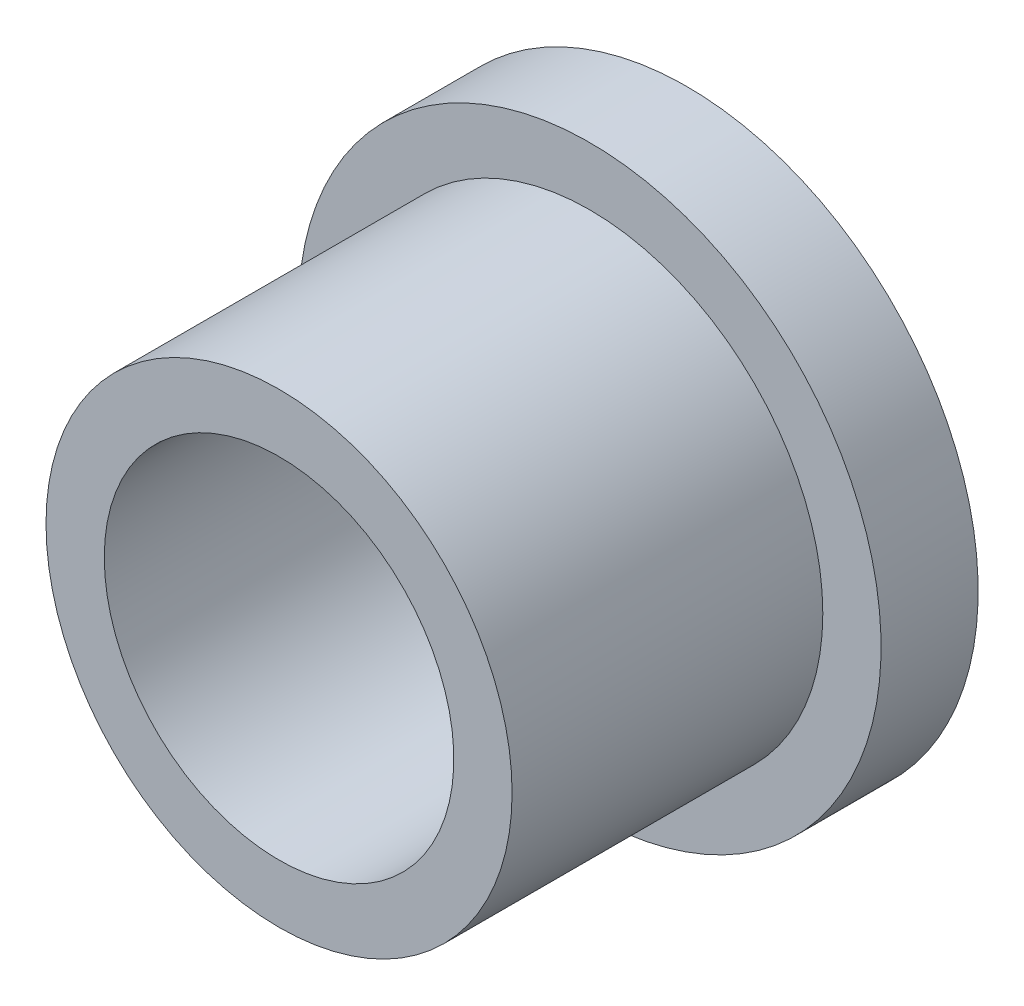
SolidWorks part; units mm, degrees
material "Hexcel AS4C (3000 Filaments)"
ref_plane "Front Plane" through (0, 0, 0) normal (0, 0, 1) x (1, 0, 0)
ref_plane "Top Plane" through (0, 0, 0) normal (0, 1, 0) x (1, 0, 0)
ref_plane "Right Plane" through (0, 0, 0) normal (1, 0, 0) x (0, 0, -1)
sketch "Sketch1" plane through (0, 0, 0) normal (0, 0, 1) x (1, 0, 0)
  circle A0 centre (0, 0) radius 15
  circle A1 centre (0, 0) radius 12
  circle A2 centre (0, 0) radius 9
  dimension "D1" = 30
  dimension "D2" = 24
  dimension "D3" = 18
extrude "Boss-Extrude1" add sketch "Sketch1" along normal blind 5 contours A0 A1 region at (-14.5757, 0, 0)
extrude "Boss-Extrude2" add sketch "Sketch1<3>" along normal blind 21 contours A1 A2 region at (-11.6606, 0, 0)
sketch "Sketch1<3>" plane through (0, 0, 0) normal (0, 0, 1) x (1, 0, 0) same geometry as "Sketch1"
